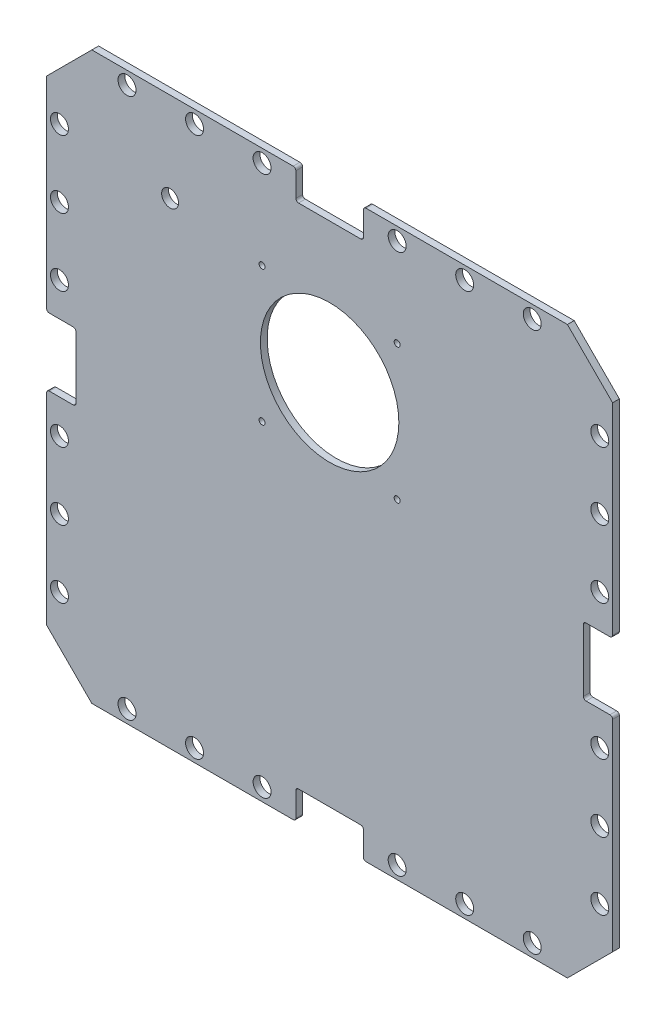
SolidWorks part; units mm, degrees
ref_plane "Front Plane" through (0, 0, 0) normal (0, 0, 1) x (1, 0, 0)
ref_plane "Top Plane" through (0, 0, 0) normal (0, 1, 0) x (1, 0, 0)
ref_plane "Right Plane" through (0, 0, 0) normal (1, 0, 0) x (0, 0, -1)
sketch "Sketch1" plane through (0, 0, 0) normal (0, 0, 1) x (1, 0, 0)
  line L0 (30.226, -4.826) -> (55.626, -4.826) construction
  line L1 (0, 0) -> (212.852, 0)
  line L2 (0, 0) -> (0, -212.852)
  line L3 (0, -212.852) -> (212.852, -212.852)
  line L4 (212.852, 0) -> (212.852, -212.852)
  line L5 (55.626, -4.826) -> (81.026, -4.826) construction
  line L6 (81.026, -4.826) -> (106.426, -4.826) construction
  line L7 (106.426, -4.826) -> (131.826, -4.826) construction
  line L8 (131.826, -4.826) -> (157.226, -4.826) construction
  line L9 (157.226, -4.826) -> (182.626, -4.826) construction
  line L10 (106.426, 0) -> (106.426, -212.852) construction
  line L11 (0, -106.426) -> (212.852, -106.426) construction
  line L12 (16.9978, 0) -> (0, -16.9978)
  line L13 (212.852, -16.9978) -> (195.8542, 0)
  line L14 (195.8542, -212.852) -> (212.852, -195.8542)
  line L15 (0, -195.8542) -> (16.9978, -212.852)
  line L16 (93.726, 0) -> (93.726, -11)
  line L17 (81.026, -38.2041) -> (131.826, -38.2042) construction
  line L18 (81.026, -38.2041) -> (81.026, -89.0042) construction
  line L19 (81.026, -89.0042) -> (131.826, -89.0042) construction
  line L20 (131.826, -38.2042) -> (131.826, -89.0042) construction
  line L21 (106.426, -89.0042) -> (106.426, -38.2041) construction
  line L22 (81.026, -63.6041) -> (131.826, -63.6041) construction
  line L23 (93.726, -11) -> (119.126, -11)
  line L24 (119.126, -11) -> (119.126, 0)
  line L25 (212.852, -93.726) -> (201.852, -93.726)
  line L26 (201.852, -93.726) -> (201.852, -119.126)
  line L27 (201.852, -119.126) -> (212.852, -119.126)
  line L28 (119.126, -212.852) -> (119.126, -201.852)
  line L29 (119.126, -201.852) -> (93.726, -201.852)
  line L30 (93.726, -201.852) -> (93.726, -212.852)
  line L31 (0, -119.126) -> (11, -119.126)
  line L32 (11, -119.126) -> (11, -93.726)
  line L33 (11, -93.726) -> (0, -93.726)
  circle A0 centre (30.226, -4.826) radius 3.38
  circle A1 centre (55.626, -4.826) radius 3.38
  circle A2 centre (81.026, -4.826) radius 3.38
  circle A3 centre (131.826, -4.826) radius 3.38
  circle A4 centre (157.226, -4.826) radius 3.38
  circle A5 centre (182.626, -4.826) radius 3.38
  circle A6 centre (106.426, -4.826) radius 5.1943
  circle A7 centre (208.026, -182.626) radius 3.38
  circle A8 centre (208.026, -157.226) radius 3.38
  circle A9 centre (208.026, -131.826) radius 3.38
  circle A10 centre (208.026, -106.426) radius 5.1943
  circle A11 centre (208.026, -81.026) radius 3.38
  circle A12 centre (208.026, -55.626) radius 3.38
  circle A13 centre (208.026, -30.226) radius 3.38
  circle A14 centre (30.226, -208.026) radius 3.38
  circle A15 centre (55.626, -208.026) radius 3.38
  circle A16 centre (81.026, -208.026) radius 3.38
  circle A17 centre (106.426, -208.026) radius 5.1943
  circle A18 centre (131.826, -208.026) radius 3.38
  circle A19 centre (157.226, -208.026) radius 3.38
  circle A20 centre (182.626, -208.026) radius 3.38
  circle A21 centre (4.826, -30.226) radius 3.38
  circle A22 centre (4.826, -55.626) radius 3.38
  circle A23 centre (4.826, -81.026) radius 3.38
  circle A24 centre (4.826, -106.426) radius 5.1943
  circle A25 centre (4.826, -131.826) radius 3.38
  circle A26 centre (4.826, -157.226) radius 3.38
  circle A27 centre (4.826, -182.626) radius 3.38
  circle A28 centre (106.426, -63.6041) radius 26.035
  circle A29 centre (81.026, -38.2041) radius 1.13
  circle A30 centre (131.826, -38.2042) radius 1.13
  circle A31 centre (131.826, -89.0042) radius 1.13
  circle A32 centre (81.026, -89.0042) radius 1.13
  circle A33 centre (46.426, -33.6041) radius 3.175
  point P14 (106.426, -106.426)
  point P69 (106.426, -106.426)
  point P78 (106.426, -106.426)
  point P88 (106.426, -11)
  point P104 (106.426, -106.426)
  point P105 (47.715, -36.3699)
  dimension "D1" = 6.76
  dimension "D5" = 10.3886
  dimension "D13" = 52.07
  dimension "D14" = 2.26
  dimension "D19" = 6.35
  dimension "D2" = 30.226
  dimension "D3" = 25.4
  dimension "D4" = 4.826
  dimension "D6" = 212.852
  dimension "D7" = 212.852
  dimension "D9" = 45
  dimension "D10" = 24.0386
  dimension "D12" = 63.6041
  dimension "D15" = 50.8
  dimension "D16" = 25.4
  dimension "D17" = 11
  dimension "D20" = 60
  dimension "D21" = 30
  dimension "D8" = 4
  dimension "D11" = 4
  dimension "D18" = 4
extrude "Boss-Extrude1" add sketch "Sketch1" along normal blind 2.54 contours A24 L2 L3 A17 L4 A10 L1 A6 A27 A26 A25 A23 A22 A21 A20 A19 A18 A16 A15 A14 A13 A12 A11 A9 A8 A7 A5 region at (106.4728, -108.7473, 0)
hole_wizard "#4-40 Tapped Hole1" positions "3DSketch1" profile "Sketch2" tap size "#4-40" standard "ANSI Inch" end condition through all
sketch3d "3DSketch1"
  line L0 (81.026, -38.2041, 2.54) -> (81.026, -38.2041, 0) construction
  line L1 (131.826, -38.2042, 2.54) -> (131.826, -38.2042, 0) construction
  line L2 (131.826, -89.0042, 2.54) -> (131.826, -89.0042, 0) construction
  line L3 (81.026, -89.0042, 2.54) -> (81.026, -89.0042, 0) construction
  point P0 (81.026, -38.2041, 2.54)
  point P4 (131.826, -38.2042, 2.54)
  point P8 (131.826, -89.0042, 2.54)
  point P12 (81.026, -89.0042, 2.54)
sketch "Sketch2" plane through (81.026, -38.2041, 2.54) normal (1, 0, 0) x (0, -1, 0)
  line L0 (0, 0) -> (0, 2.54)
  line L1 (0, 2.54) -> (1.1303, 2.54)
  line L2 (1.1303, 2.54) -> (1.1303, 0)
  line L5 (1.1303, 0) -> (0, 0)
  line L11 (0, -6.35) -> (0, 107.95) construction
  dimension "Thru Tap Drill Dia." = 2.2606
  dimension "Thru Tap Drill Depth" = 2.54
cosmetic thread "Hole Thread1" parameters "D2"=2.8448
cosmetic thread "Hole Thread2" parameters "D2"=2.8448
cosmetic thread "Hole Thread3" parameters "D2"=2.8448
cosmetic thread "Hole Thread4" parameters "D2"=2.8448
fillet "Fillet1" radius 1 16 edges at (0, -93.726, 1.27) (11, -93.726, 1.27) (0, -119.126, 1.27) (11, -119.126, 1.27) (93.726, -212.852, 1.27) (93.726, -201.852, 1.27) (119.126, -212.852, 1.27) (119.126, -201.852, 1.27) (212.852, -119.126, 1.27) (201.852, -119.126, 1.27) (212.852, -93.726, 1.27) (201.852, -93.726, 1.27) (119.126, -11, 1.27) (119.126, 0, 1.27) (93.726, -11, 1.27) (93.726, 0, 1.27)
